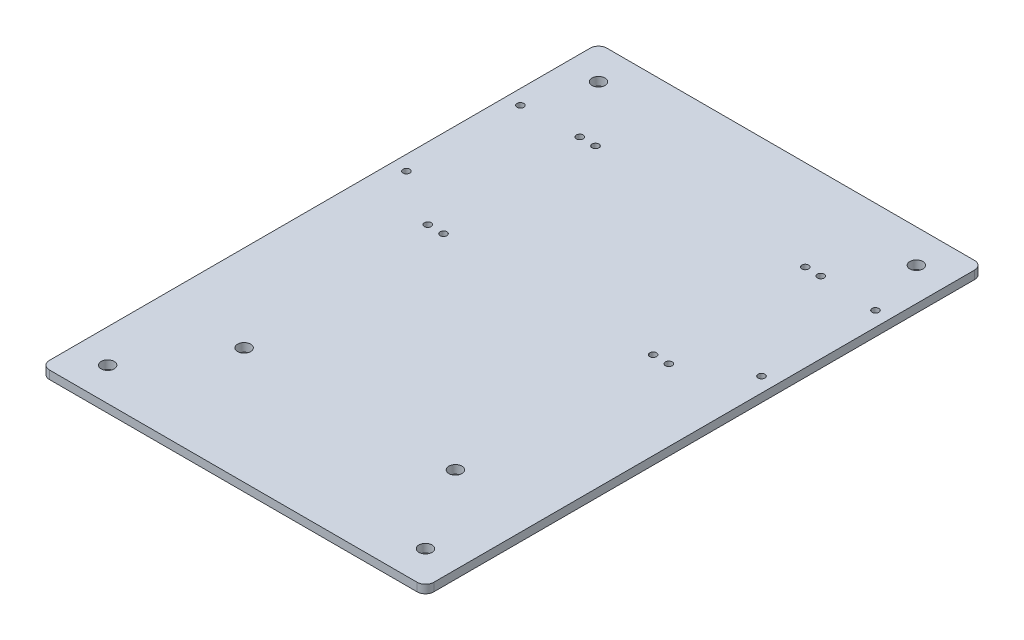
SolidWorks part; units mm, degrees
ref_plane "Front Plane" through (0, 0, 0) normal (0, 0, 1) x (1, 0, 0)
ref_plane "Top Plane" through (0, 0, 0) normal (0, 1, 0) x (1, 0, 0)
ref_plane "Right Plane" through (0, 0, 0) normal (1, 0, 0) x (0, 0, -1)
sketch "Sketch1" plane through (0, 0, 0) normal (0, 1, 0) x (1, 0, 0)
  line L1 (-60.6425, -93.6625) -> (60.6425, -93.6625) construction
  line L2 (-60.6425, -93.6625) -> (-60.6425, 93.6625) construction
  line L3 (-60.6425, 93.6625) -> (60.6425, 93.6625) construction
  line L4 (60.6425, -93.6625) -> (60.6425, 93.6625) construction
  line L5 (-60.6425, -93.6625) -> (60.6425, 93.6625) construction
  line L6 (-60.6425, 93.6625) -> (60.6425, -93.6625) construction
  line L7 (-73.3425, -106.3625) -> (73.3425, -106.3625)
  line L8 (-73.3425, -106.3625) -> (-73.3425, 106.3625)
  line L9 (-73.3425, 106.3625) -> (73.3425, 106.3625)
  line L10 (73.3425, -106.3625) -> (73.3425, 106.3625)
  line L11 (-73.3425, -106.3625) -> (73.3425, 106.3625) construction
  line L12 (-73.3425, 106.3625) -> (73.3425, -106.3625) construction
  circle A0 centre (-60.6425, 93.6625) radius 2.4892
  circle A1 centre (60.6425, 93.6625) radius 2.4892
  circle A2 centre (60.6425, -93.6625) radius 2.4892
  circle A3 centre (-60.6425, -93.6625) radius 2.4892
  point P0 (0, 0)
  point P11 (0, 0)
  dimension "D1" = 4.9784
  dimension "D2" = 121.285
  dimension "D3" = 187.325
  dimension "D4" = 12.7
  dimension "D5" = 12.7
extrude "Boss-Extrude1" add sketch "Sketch1" along normal mid plane 3.175
fillet "Fillet1" radius 3.175 4 edges at (-73.3425, 0, 106.3625) (-73.3425, 0, -106.3625) (73.3425, 0, -106.3625) (73.3425, 0, 106.3625)
sketch "Sketch2" plane through (0, 1.5875, 0) normal (0, 1, 0) x (1, 0, 0)
  line L1 (-46, 13.8625) -> (46, 13.8625) construction
  line L2 (-46, 13.8625) -> (-46, 71.8625) construction
  line L3 (-46, 71.8625) -> (46, 71.8625) construction
  line L4 (46, 13.8625) -> (46, 71.8625) construction
  line L5 (-46, 13.8625) -> (46, 71.8625) construction
  line L6 (-46, 71.8625) -> (46, 13.8625) construction
  line L7 (70.1675, 106.3625) -> (-70.1675, 106.3625) construction
  line L9 (-40, 13.8625) -> (40, 13.8625) construction
  line L10 (-40, 13.8625) -> (-40, 71.8625) construction
  line L11 (-40, 71.8625) -> (40, 71.8625) construction
  line L12 (40, 13.8625) -> (40, 71.8625) construction
  line L13 (-40, 13.8625) -> (40, 71.8625) construction
  line L14 (-40, 71.8625) -> (40, 13.8625) construction
  circle A0 centre (-46, 71.8625) radius 1.3
  circle A1 centre (-46, 13.8625) radius 1.3
  circle A2 centre (46, 71.8625) radius 1.3
  circle A3 centre (46, 13.8625) radius 1.3
  circle A4 centre (-40, 71.8625) radius 1.3
  circle A5 centre (-40, 13.8625) radius 1.3
  circle A6 centre (40, 13.8625) radius 1.3
  circle A7 centre (40, 71.8625) radius 1.3
  point P0 (0, 42.8625)
  point P16 (0, 42.8625)
  dimension "D2" = 2.6
  dimension "D1" = 46
  dimension "D3" = 58
  dimension "D4" = 63.5
  dimension "D5" = 40
extrude "Cut-Extrude1" cut sketch "Sketch2" against normal through all contours A6 | A7 | A0 | A1 | A3 | A2 | A4 | A5 region at (40, 1.5875, -13.8625) region at (40, 1.5875, -71.8625)
sketch "Sketch3" plane through (0, 1.5875, 0) normal (0, 1, 0) x (1, 0, 0)
  line L0 (70.1675, 106.3625) -> (-70.1675, 106.3625) construction
  line L1 (-67.75, 70.9625) -> (67.75, 70.9625) construction
  line L2 (-67.75, 70.9625) -> (-67.75, 27.4625) construction
  line L3 (-67.75, 27.4625) -> (67.75, 27.4625) construction
  line L4 (67.75, 70.9625) -> (67.75, 27.4625) construction
  line L5 (-67.75, 70.9625) -> (67.75, 27.4625) construction
  line L6 (-67.75, 27.4625) -> (67.75, 70.9625) construction
  circle A0 centre (67.75, 70.9625) radius 1.3
  circle A1 centre (-67.75, 70.9625) radius 1.3
  circle A2 centre (-67.75, 27.4625) radius 1.3
  circle A3 centre (67.75, 27.4625) radius 1.3
  point P0 (0, 49.2125)
  dimension "D3" = 2.6
  dimension "D1" = 135.5
  dimension "D2" = 43.5
  dimension "D4" = 57.15
extrude "Cut-Extrude2" cut sketch "Sketch3" against normal through all
sketch "Sketch4" plane through (0, 1.5875, 0) normal (0, 1, 0) x (1, 0, 0)
  line L0 (40.3225, -61.9125) -> (-40.3225, -61.9125) construction
  line L1 (-70.1675, -106.3625) -> (70.1675, -106.3625) construction
  circle A0 centre (-40.3225, -61.9125) radius 2.4892
  circle A1 centre (40.3225, -61.9125) radius 2.4892
  point P3 (0, -61.9125)
  dimension "D2" = 4.9784
  dimension "D1" = 80.645
  dimension "D3" = 44.45
extrude "Cut-Extrude3" cut sketch "Sketch4" against normal through all
